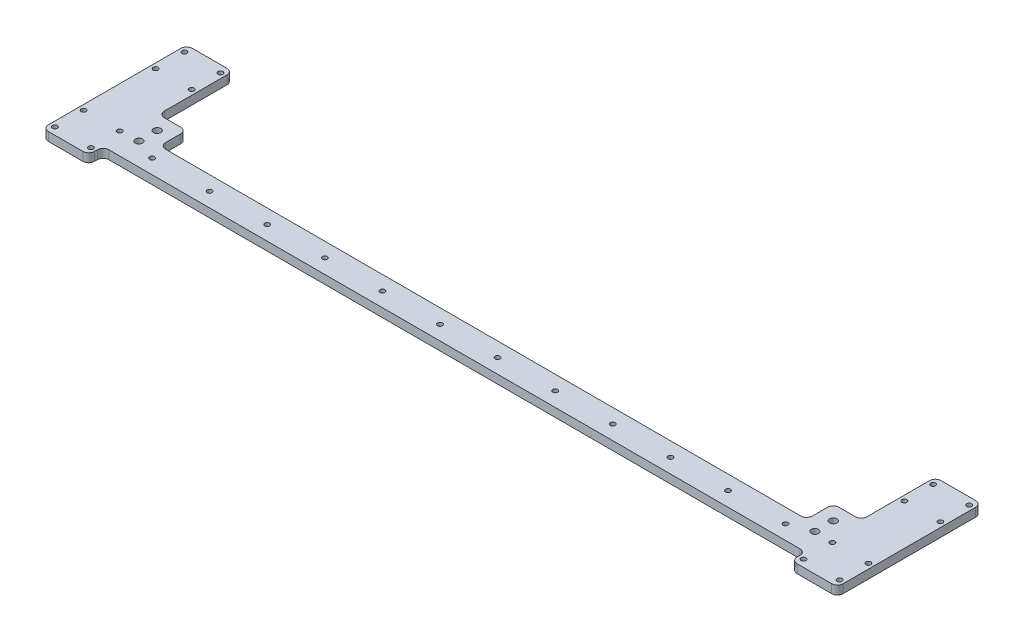
SolidWorks part; units mm, degrees
ref_plane "Front Plane" through (0, 0, 0) normal (0, 0, 1) x (1, 0, 0)
ref_plane "Top Plane" through (0, 0, 0) normal (0, 1, 0) x (1, 0, 0)
ref_plane "Right Plane" through (0, 0, 0) normal (1, 0, 0) x (0, 0, -1)
sketch "Sketch1" plane through (0, 0, 0) normal (0, 1, 0) x (1, 0, 0)
  line L1 (0, 0) -> (552, 0)
  line L2 (0, 0) -> (0, 20)
  line L3 (0, 20) -> (552, 20)
  line L4 (552, 0) -> (552, 20)
  dimension "D1" = 20
  dimension "D2" = 552
extrude "Boss-Extrude1" add sketch "Sketch1" along normal blind 6
ref_plane "Plane1" through (276, 0, 0) normal (1, 0, 0) x (0, 0, -1)
sketch "Sketch3" plane through (0, 0, 0) normal (0, -1, 0) x (1, 0, 0)
  line L0 (0, 0) -> (552, 0) construction
  line L1 (0, -90) -> (32, -90)
  line L2 (0, -90) -> (0, 10)
  line L3 (0, 10) -> (32, 10)
  line L4 (32, -90) -> (32, 10)
  dimension "D1" = 32
  dimension "D2" = 100
  dimension "D3" = 10
extrude "Boss-Extrude2" add sketch "Sketch3" against normal up to surface (6 mm away) up to face at (276, 6, -10)
sketch "Sketch4" plane through (0, 6, 0) normal (0, 1, 0) x (1, 0, 0)
  line L0 (16, -10) -> (16, 90)
  line L1 (0, -10) -> (32, -10) construction
  line L2 (32, 90) -> (0, 90) construction
  line L4 (3.5, -5) -> (28.5, -5)
  line L5 (3.5, -5) -> (3.5, 15)
  line L6 (3.5, 15) -> (28.5, 15)
  line L7 (28.5, -5) -> (28.5, 15)
  line L8 (3.5, -5) -> (28.5, 15) construction
  line L9 (3.5, 15) -> (28.5, -5) construction
  line L10 (3.5, 65) -> (28.5, 65)
  line L11 (3.5, 65) -> (3.5, 85)
  line L12 (3.5, 85) -> (28.5, 85)
  line L13 (28.5, 65) -> (28.5, 85)
  line L14 (3.5, 65) -> (28.5, 85) construction
  line L15 (3.5, 85) -> (28.5, 65) construction
  point P6 (16, 5)
  point P11 (16, 75)
  dimension "D1" = 20
  dimension "D2" = 25
  dimension "D3" = 5
  dimension "D4" = 5
sketch "Sketch7" plane through (0, 6, 0) normal (0, 1, 0) x (1, 0, 0)
  line L0 (276, 0) -> (276, 20) construction
  line L1 (32, 0) -> (552, 0) construction
  line L2 (552, 20) -> (32, 20) construction
  line L3 (276, -3.3) -> (276, 3.3) construction
  line L4 (276, 10) -> (256, 10) construction
  point P11 (256, 10)
  point P13 (216, 10)
  point P14 (176, 10)
  point P15 (136, 10)
  point P16 (96, 10)
  point P17 (56, 10)
  dimension "D1" = 20
  dimension "D3" = 40
  dimension "D2" = 6
hole_wizard "M3 Clearance Hole1" positions "Sketch5" profile "Sketch6" hole size "M3" standard "ANSI Metric" end condition through all
sketch "Sketch5" plane through (0, 6, 0) normal (0, 1, 0) x (1, 0, 0)
  point P0 (3.5, -5)
  point P3 (3.5, 15)
  point P6 (28.5, 15)
  point P9 (28.5, -5)
  point P12 (3.5, 85)
  point P15 (28.5, 85)
  point P18 (28.5, 65)
  point P21 (3.5, 65)
  point P25 (56, 10)
  point P28 (96, 10)
  point P31 (136, 10)
  point P34 (176, 10)
  point P37 (216, 10)
  point P40 (256, 10)
sketch "Sketch6" plane through (3.5, 6, 5) normal (1, 0, 0) x (0, 0, 1)
  line L0 (0, 0) -> (0, 6)
  line L1 (0, 6) -> (1.7, 6)
  line L2 (1.7, 6) -> (1.7, 0)
  line L5 (1.7, 0) -> (0, 0)
  line L11 (0, -6.35) -> (0, 107.95) construction
  dimension "Thru Hole Dia." = 3.4
  dimension "Thru Hole Depth" = 6
sketch "Sketch8" plane through (0, 6, 0) normal (0, 1, 0) x (1, 0, 0)
  line L0 (56.3721, 22) -> (87.6482, 22) construction
  line L1 (552, 20) -> (32, 20) construction
  line L2 (105.1095, -2) -> (88.5975, -2) construction
  line L3 (32, 0) -> (552, 0) construction
  line L4 (34.8662, 90) -> (34.8662, 28.3662) construction
  line L5 (34.8662, -10) -> (34.8662, -8.3662) construction
  line L6 (28.5, -10) -> (28.5, 90) construction
  line L7 (0, -10) -> (32, -10) construction
  line L8 (32, 90) -> (0, 90) construction
  line L9 (28.5, 65) -> (28.5, 85) construction
  circle A0 centre (41.2324, 28.3662) radius 6.3662
  circle A1 centre (28.5, 90) radius 6.3662
  circle A2 centre (28.5, -10) radius 6.3662
  circle A3 centre (41.2324, -8.3662) radius 6.3662
  circle A4 centre (41.2324, 28.3662) radius 10.16
  circle A5 centre (41.2324, -8.3662) radius 10.16
  circle A6 centre (28.5, -10) radius 10.16
  circle A7 centre (28.5, 90) radius 10.16
  dimension "D3" = 12.7324
  dimension "D4" = 20.32
  dimension "D1" = 2
  dimension "D2" = 2
sketch "Sketch10" plane through (0, 6, 0) normal (0, 1, 0) x (1, 0, 0)
  line L5 (32, 20) -> (51.3924, 20)
  line L6 (32, 20) -> (32, 38.5262)
  line L7 (32, 38.5262) -> (51.3924, 38.5262)
  line L8 (51.3924, 20) -> (51.3924, 38.5262)
  circle A2 centre (41.2324, 28.3662) radius 2.525
  point P0 (41.2324, 28.3662)
  dimension "D1" = 5.05
  dimension "D2" = 18.5262
  dimension "D3" = 19.3924
extrude "Boss-Extrude3" add sketch "Sketch10" against normal up to surface (6 mm away) up to face at (3.5, 0, 6.7)
sketch "Sketch12" plane through (0, 6, 0) normal (0, 1, 0) x (1, 0, 0)
  line L0 (41.2324, 28.3662) -> (41.2324, 15.6362) construction
  circle A0 centre (41.2324, 15.6362) radius 2.525
  circle A2 centre (41.2324, 28.3662) radius 2.525 construction
  dimension "D1" = 12.73
extrude "Cut-Extrude2" cut sketch "Sketch12" against normal through all
fillet "Fillet2" radius 4 8 edges at (32, 3, 10) (0, 3, 10) (0, 3, -90) (32, 3, -90) (32, 3, -38.5262) (51.3924, 3, -38.5262) (51.3924, 3, -20) (32, 3, 0)
mirror "Mirror1" about plane through (276, 0, 0) normal (1, 0, 0) of "Cut-Extrude2", "Boss-Extrude2", "M3 Clearance Hole1", "Boss-Extrude3", "Fillet2"
